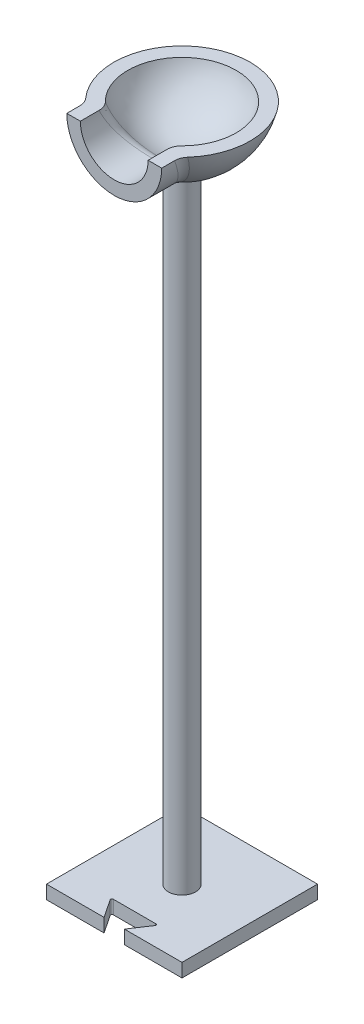
SolidWorks part; units mm, degrees
note: The reader was unsure of these and kept them because the rebuilt part matched: shared geometry of "Sketch5<3>".
ref_plane "Front Plane" through (0, 0, 0) normal (0, 0, 1) x (1, 0, 0)
ref_plane "Top Plane" through (0, 0, 0) normal (0, 1, 0) x (1, 0, 0)
ref_plane "Right Plane" through (0, 0, 0) normal (1, 0, 0) x (0, 0, -1)
sketch "Sketch1" plane through (0, 0, 0) normal (0, 1, 0) x (1, 0, 0)
  line L1 (-50, -50) -> (50, -50)
  line L2 (-50, -50) -> (-50, 50)
  line L3 (-50, 50) -> (50, 50)
  line L4 (50, -50) -> (50, 50)
  line L5 (-50, -50) -> (50, 50) construction
  line L6 (-50, 50) -> (50, -50) construction
  point P0 (0, 0)
  dimension "D1" = 100
extrude "Boss-Extrude1" add sketch "Sketch1" along normal blind 10
sketch "Sketch3" plane through (0, 0, 0) normal (1, 0, 0) x (0, 0, -1)
  line L0 (0, 10) -> (0, 510) construction
  line L1 (-50, 10) -> (50, 10) construction
  line L2 (0, 510) -> (40, 510) construction
  line L4 (50, 10) -> (50, 0) construction
  line L5 (0, 480) -> (0, 470)
  line L7 (40, 510) -> (50.3322, 510)
  line L8 (0, 470) -> (0, 10)
  line L9 (0, 10) -> (10, 10)
  line L10 (10, 10) -> (10, 470.977)
  arc A0 (0, 480) -> (40, 510) centre (0, 521.6667) ccw
  arc A1 (10, 470.977) -> (50.3322, 510) centre (0, 521.6667) ccw
  arc A2 (0, 470) -> (49.6, 507.2) centre (0, 521.6667) ccw construction
  dimension "D1" = 500
  dimension "D2" = 30
  dimension "D3" = 10
  dimension "D5" = 20
  dimension "D4" = 10
revolve "Revolve1" add sketch "Sketch3" angle 360 about L0
sketch "Sketch5" plane through (0, 0, 0) normal (0, 0, 1) x (1, 0, 0)
  line L0 (40, 510) -> (-40, 510) construction
  line L1 (25, 510) -> (-25, 510) construction
  line L2 (25, 510) -> (35, 510)
  line L3 (-25, 510) -> (-35, 510)
  line L4 (-25, 510) -> (25, 510)
  arc A0 (25, 510) -> (-25, 510) centre (0, 510) cw
  arc A1 (35, 510) -> (-35, 510) centre (0, 510) cw
  arc A2 (25, 510) -> (-25, 510) centre (0, 510) cw construction
  dimension "D1" = 25
  dimension "D2" = 10
extrude "Cut-Extrude2" cut sketch "Sketch5" along normal through all contours A0 L4
extrude "Boss-Extrude2" add sketch "Sketch5<3>" along normal up to surface (18.775 mm away) from vertex at 31.225 contours A1 L2 A0 L3 up to face at (0, 5, 50)
sketch "Sketch5<3>" plane through (0, 0, 0) normal (0, 0, 1) x (1, 0, 0) same geometry as "Sketch5"
sketch "Sketch7" plane through (0, 0, 31.225) normal (0, 0, -1) x (-1, 0, 0)
  arc A2 (-31.9518, 495.7143) -> (31.9518, 495.7143) centre (0, 521.6667) ccw
  arc A3 (-31.9518, 495.7143) -> (31.9518, 495.7143) centre (0, 510) ccw
  arc A4 (-31.9518, 495.7143) -> (31.9518, 495.7143) centre (0, 521.6667) ccw
  arc A5 (-31.9518, 495.7143) -> (31.9518, 495.7143) centre (0, 510) ccw
  dimension "D1" = 0
extrude "Boss-Extrude3" add sketch "Sketch7" along normal up to next
fillet "Fillet2" radius 10 2 edges at (-4.6158, 485.4298, 20.0423) (-3.3969, 475.1652, 22.2603)
sketch "Sketch2" plane through (6.1604, 10, 46.5264) normal (0, 1, 0) x (1, 0, 0)
  line L0 (1.3396, -3.4736) -> (11.3396, 11.5264)
  line L1 (-56.1604, -3.4736) -> (43.8396, -3.4736) construction
  line L2 (11.3396, 11.5264) -> (-23.6604, 11.5264)
  line L3 (-23.6604, 11.5264) -> (-13.6604, -3.4736)
  line L4 (-13.6604, -3.4736) -> (1.3396, -3.4736)
  line L5 (-6.1604, 11.5264) -> (-6.1604, -19.897) construction
  line L6 (-6.1604, -3.4736) -> (-6.1604, 11.5264) construction
  dimension "D1" = 15
  dimension "D2" = 35
  dimension "D3" = 15
  dimension "D4" = 0
extrude "Cut-Extrude1" cut sketch "Sketch2" against normal up to next (10 mm away)
fillet "Fillet1" radius 1 2 edges at (-17.5, 5, 35) (17.5, 5, 35)
other "Female-Slot<1>"
equation "\"height\"= 10"
equation "\"D1@Sketch3\"=\"height\"*50"
